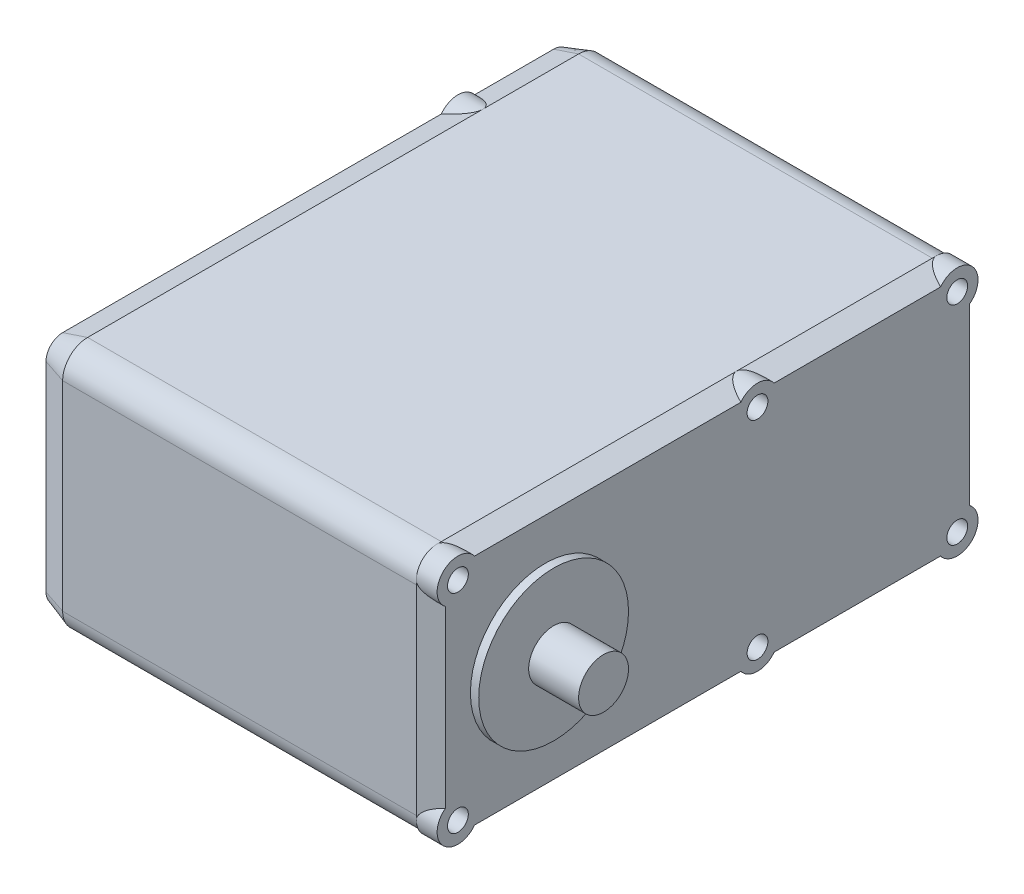
SolidWorks part; units mm, degrees
ref_plane "Front Plane" through (0, 0, 0) normal (0, 0, 1) x (1, 0, 0)
ref_plane "Top Plane" through (0, 0, 0) normal (0, 1, 0) x (1, 0, 0)
ref_plane "Right Plane" through (0, 0, 0) normal (1, 0, 0) x (0, 0, -1)
sketch "Sketch1" plane through (0, 0, 0) normal (0, 1, 0) x (1, 0, 0)
  line L1 (24, -32.5) -> (-24, -32.5)
  line L2 (24, -32.5) -> (24, 32.5)
  line L3 (24, 32.5) -> (-24, 32.5)
  line L4 (-24, -32.5) -> (-24, 32.5)
  line L5 (24, -32.5) -> (-24, 32.5) construction
  line L6 (24, 32.5) -> (-24, -32.5) construction
  point P0 (0, 0)
extrude "Boss-Extrude1" add sketch "Sketch1" along normal blind 30
fillet "Fillet2" radius 3 4 edges at (0, 30, -32.5) (0, 0, -32.5) (0, 0, 32.5) (0, 30, 32.5)
sketch "Sketch2" plane through (-24, 0, 0) normal (-1, 0, 0) x (0, 0, 1)
  line L0 (32.5, 15) -> (19.5, 15) construction
  line L1 (32.5, 27) -> (32.5, 3) construction
  circle A0 centre (19.5, 15) radius 9
extrude "Boss-Extrude2" add sketch "Sketch2" along normal blind 1
sketch "Sketch3" plane through (-25, 0, 0) normal (-1, 0, 0) x (0, 0, 1)
  line L0 (15.5, 15) -> (23.5, 15) construction
  line L1 (19.5, 19) -> (19.5, 11) construction
  circle A0 centre (19.5, 15) radius 4 construction
  point P6 (19.5, 15)
  point P9 (19.5, 15)
sketch "Sketch4" plane through (24, 0, 0) normal (1, 0, 0) x (0, 0, -1)
  circle A0 centre (-19.5, 15) radius 9 construction
  circle A1 centre (-19.5, 15) radius 9
extrude "Boss-Extrude4" add sketch "Sketch4" along normal blind 1
sketch "Sketch5" plane through (25, 0, 0) normal (1, 0, 0) x (0, 0, -1)
  circle A0 centre (-19.5, 15) radius 3
extrude "Boss-Extrude5" add sketch "Sketch5" along normal blind 6
chamfer "Chamfer1" distance 3 angle 18.435 8 edges at (-24, 0, 0) (-24, 29.1213, -31.6213) (-24, 15, -32.5) (-24, 0.8787, -31.6213) (-24, 30, 0) (-24, 29.1213, 31.6213) (-24, 15, 32.5) (-24, 0.8787, 31.6213) first distance on face at (0, 0, 0) first distance on face at (0, 28.8107, -31.3107) first distance on face at (0, 15, -32.5) first distance on face at (0, 1.1893, -31.3107) first distance on face at (0, 30, 0) first distance on face at (0, 28.8107, 31.3107) first distance on face at (0, 15, 32.5) first distance on face at (0, 1.1893, 31.3107)
chamfer "Chamfer2" distance 1 angle 45 1 edges at (-25, 15, 28.5)
chamfer "Chamfer3" distance 2.5 angle 21.8 8 edges at (24, 0.8787, -31.6213) (24, 15, -32.5) (24, 29.1213, -31.6213) (24, 30, 0) (24, 29.1213, 31.6213) (24, 15, 32.5) (24, 0.8787, 31.6213) (24, 0, 0) first distance on face at (1.5, 1.1893, -31.3107) first distance on face at (1.5, 15, -32.5) first distance on face at (1.5, 28.8107, -31.3107) first distance on face at (1.5, 30, 0) first distance on face at (1.5, 28.8107, 31.3107) first distance on face at (1.5, 15, 32.5) first distance on face at (1.5, 1.1893, 31.3107) first distance on face at (1.5, 0, 0)
sketch "Sketch6" plane through (24, 0, 0) normal (1, 0, 0) x (0, 0, -1)
  line L0 (32.5, 27) -> (32.5, 3) construction
  line L1 (-29.5, 30) -> (29.5, 30) construction
  line L2 (29.5, 0) -> (-29.5, 0) construction
  line L3 (6, 27.5) -> (30, 27.5) construction
  line L4 (30, 27.5) -> (30, 2.5) construction
  line L5 (-30, 2.5) -> (-30, 27.5) construction
  line L8 (-32.5, 3) -> (-32.5, 27) construction
  circle A4 centre (6, 27.5) radius 2.5
  circle A5 centre (6, 2.5) radius 2.5
  circle A6 centre (30, 27.5) radius 2.5
  circle A7 centre (-30, 27.5) radius 2.5
  circle A9 centre (30, 2.5) radius 2.5
  circle A10 centre (-30, 2.5) radius 2.5
  point P11 (0, 0)
extrude "Boss-Extrude6" add sketch "Sketch6" against normal blind 2.5
sketch "Sketch7" plane through (-24, 0, 0) normal (-1, 0, 0) x (0, 0, 1)
  line L0 (-32.5, 3) -> (-32.5, 27) construction
  line L2 (-31.5, 27) -> (-31.5, 3) construction
  line L3 (-30, 15) -> (-31.5, 15) construction
  line L4 (-30, 15) -> (-30, 2.5) construction
  line L5 (-30, 2.5) -> (-18, 2.5) construction
  line L6 (29.5, 0) -> (-29.5, 0) construction
  line L7 (-30, 15) -> (-30, 27.5) construction
  line L8 (-30, 27.5) -> (-18, 27.5) construction
  line L9 (-29.5, 30) -> (29.5, 30) construction
  circle A0 centre (-30, 15) radius 2.5
  circle A1 centre (-18, 2.5) radius 2.5
  circle A2 centre (-18, 27.5) radius 2.5
  point P17 (0, 0)
  dimension "D1" = 12.5
  dimension "D3" = 12.5
extrude "Boss-Extrude7" add sketch "Sketch7" against normal blind 3
sketch "Sketch8" plane through (-24, 0, 0) normal (-1, 0, 0) x (0, 0, 1)
  circle A0 centre (-18, 27.5) radius 1.25
  circle A1 centre (-30, 15) radius 1.25
  circle A2 centre (-18, 2.5) radius 1.25
extrude "Cut-Extrude1" cut sketch "Sketch8" against normal blind 5
sketch "Sketch10" plane through (24, 0, 0) normal (1, 0, 0) x (0, 0, -1)
  circle A0 centre (6, 2.5) radius 1.25
  circle A1 centre (30, 2.5) radius 1.25
  circle A2 centre (6, 27.5) radius 1.25
  circle A3 centre (30, 27.5) radius 1.25
  circle A4 centre (-30, 2.5) radius 1.25
  circle A5 centre (-30, 27.5) radius 1.25
extrude "Cut-Extrude2" cut sketch "Sketch10" against normal blind 5
